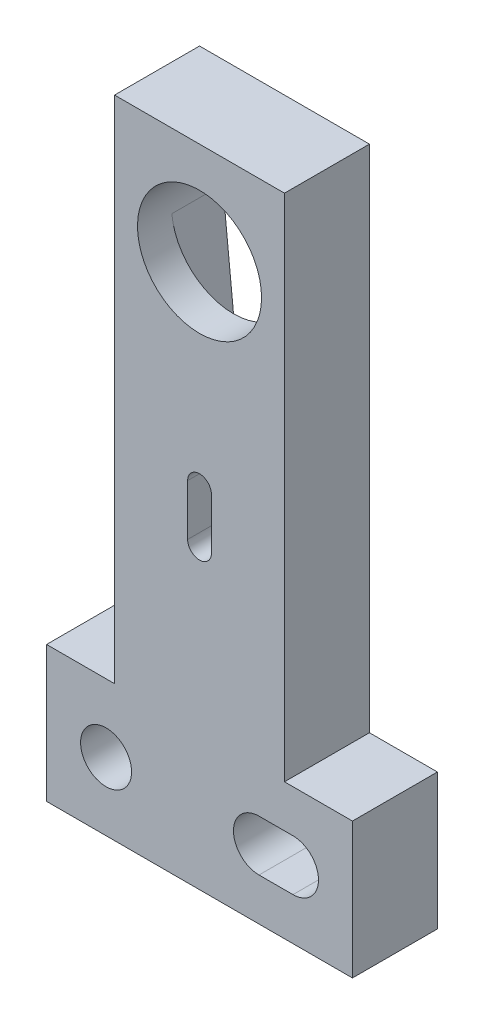
SolidWorks part; units mm, degrees
ref_plane "Plano frontal" through (0, 0, 0) normal (0, 0, 1) x (1, 0, 0)
ref_plane "Plano superior" through (0, 0, 0) normal (0, 1, 0) x (1, 0, 0)
ref_plane "Plano direito" through (0, 0, 0) normal (1, 0, 0) x (0, 0, -1)
sketch "Esboço1" plane through (0, 0, 0) normal (0, 0, 1) x (1, 0, 0)
  line L0 (0, 0) -> (0, -30) construction
  line L1 (-5, 0) -> (-5, -30)
  line L2 (5, 0) -> (5, -30)
  line L3 (-5, -30) -> (-9, -30)
  line L4 (-9, -30) -> (-9, -38)
  line L5 (-9, -38) -> (9, -38)
  line L6 (9, -38) -> (9, -30)
  line L7 (9, -30) -> (5, -30)
  line L8 (-5, 0) -> (5, 0)
  line L9 (2.2387, -20.225) -> (3.6317, -6.365)
  line L10 (-3.6317, -6.365) -> (-2.2387, -20.225)
  line L11 (0, -20.5) -> (0, -17.5) construction
  line L12 (-0.7, -20.5) -> (-0.7, -17.5)
  line L13 (0.7, -20.5) -> (0.7, -17.5)
  line L14 (5.5, -32.5) -> (3.5, -32.5)
  line L16 (3.5, -35.5) -> (5.5, -35.5)
  circle A0 centre (-5.5, -34) radius 1.5
  arc A1 (5.5, -35.5) -> (5.5, -32.5) centre (5.5, -34) ccw
  circle A2 centre (0, -6) radius 3.65
  arc A3 (-2.2387, -20.225) -> (2.2387, -20.225) centre (0, -20) ccw
  arc A4 (-0.7, -20.5) -> (0.7, -20.5) centre (0, -20.5) ccw
  arc A5 (0.7, -17.5) -> (-0.7, -17.5) centre (0, -17.5) ccw
  arc A6 (3.5, -32.5) -> (3.5, -35.5) centre (3.5, -34) ccw
  point P15 (-9, -34)
  point P25 (0, -19)
  dimension "D3" = 3
  dimension "D8" = 7.3
  dimension "D11" = 4.5
  dimension "D12" = 0.7
  dimension "D4" = 8
  dimension "D5" = 8
  dimension "D6" = 18
  dimension "D7" = 30
  dimension "D9" = 6
  dimension "D10" = 14
  dimension "D13" = 3
  dimension "D14" = 0.5
  dimension "D15" = 2
  dimension "D1" = 5
  dimension "D2" = 5
extrude "Ressalto-extrusão1" add sketch "Esboço1" along normal blind 5 contours L8 L1 L3 L4 L5 L6 L7 L2 A2 L9 A3 L10 A1 A0 | L0 A2 L10 A3 | A2 L0 A3 L9 region at (-0.0639, -23.7789, 0) region at (1.5336, -14.5081, 0) region at (-1.5336, -14.5081, 0)
extrude "Corte-extrusão1" cut sketch "Esboço1<3>" along normal blind 3 contours L10 A3 L9 A2 A5 L13 A4 L12 region at (0, -14.5081, 0)
sketch "Esboço1<3>" plane through (0, 0, 0) normal (0, 0, 1) x (1, 0, 0) same geometry as "Esboço1"
equation "\"D2@Esboço1\"=\"D1@Esboço1\""
